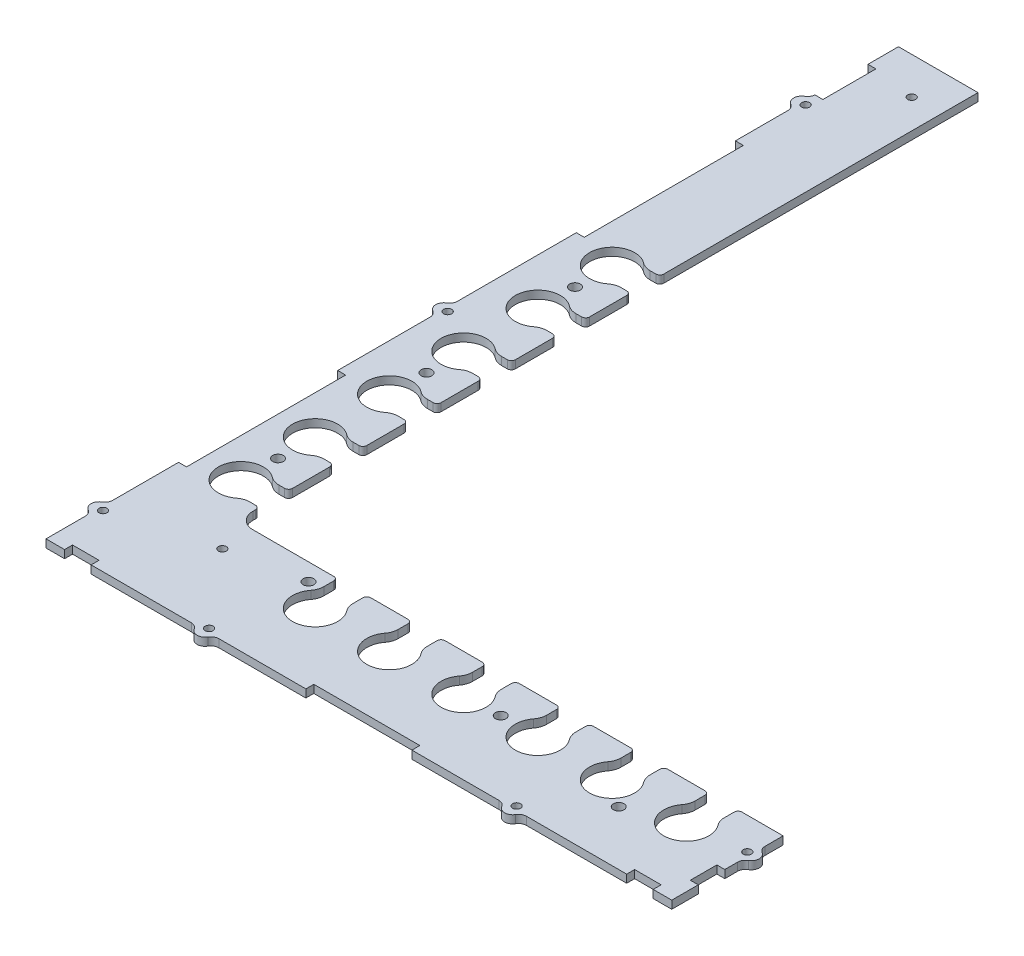
SolidWorks part; units mm, degrees
ref_plane "Спереди" through (0, 0, 0) normal (0, 0, 1) x (1, 0, 0)
ref_plane "Сверху" through (0, 0, 0) normal (0, 1, 0) x (1, 0, 0)
ref_plane "Справа" through (0, 0, 0) normal (1, 0, 0) x (0, 0, -1)
sketch "Эскиз1" plane through (0, 0, 0) normal (0, 1, 0) x (1, 0, 0)
  line L0 (0, 0) -> (0, 321.5)
  line L1 (0, 321.5) -> (30, 321.5)
  line L2 (30, 321.5) -> (30, 42)
  line L3 (30, 42) -> (236, 42)
  line L4 (236, 42) -> (236, 0)
  line L5 (236, 0) -> (0, 0)
  dimension "D1" = 321.5
  dimension "D2" = 236
  dimension "D3" = 42
  dimension "D4" = 30
extrude "Бобышка-Вытянуть1" add sketch "Эскиз1" along normal blind 3
sketch "Эскиз2" plane through (0, 3, 0) normal (0, 1, 0) x (1, 0, 0)
  line L0 (236, 0) -> (236, 42) construction
  line L1 (236, 10) -> (233, 10)
  line L2 (236, 10) -> (236, 20)
  line L3 (236, 20) -> (233, 20)
  line L4 (233, 10) -> (233, 20)
  dimension "D1" = 3
  dimension "D2" = 10
  dimension "D3" = 10
extrude "Вырез-Вытянуть1" cut sketch "Эскиз2" against normal blind 3
sketch "Эскиз4" plane through (236, 0, 0) normal (1, 0, 0) x (0, 0, -1)
  line L0 (20, 3) -> (42, 3) construction
  line L1 (20, 0) -> (42, 0) construction
  line L2 (30, 0) -> (33, 0)
  line L3 (30, 0) -> (30, 3)
  line L4 (30, 3) -> (33, 3)
  line L5 (33, 0) -> (33, 3)
  dimension "D1" = 30
  dimension "D2" = 3
revolve "Повернуть1" add sketch "Эскиз4" angle 360 about L3
fillet "Скругление1" radius 3 2 edges at (236, 1.5, -27) (236, 1.5, -33)
sketch "Эскиз5" plane through (0, 3, 0) normal (0, 1, 0) x (1, 0, 0)
  circle A0 centre (234.5, 30) radius 1.5
  dimension "D1" = 3
  dimension "D2" = 30
  dimension "D3" = 1.5
extrude "Вырез-Вытянуть2" cut sketch "Эскиз5" against normal blind 3
sketch "Эскиз6" plane through (0, 3, 0) normal (0, 1, 0) x (1, 0, 0)
  line L0 (0, 0) -> (236, 0) construction
  line L1 (229, 0) -> (219, 0)
  line L2 (229, 0) -> (229, 3)
  line L3 (229, 3) -> (219, 3)
  line L4 (219, 0) -> (219, 3)
  line L5 (118, 0) -> (118, 12.6976) construction
  line L6 (17, 0) -> (17, 3)
  line L7 (7, 3) -> (17, 3)
  line L8 (7, 0) -> (7, 3)
  line L9 (7, 0) -> (17, 0)
  dimension "D1" = 10
  dimension "D2" = 7
  dimension "D3" = 3
extrude "Вырез-Вытянуть3" cut sketch "Эскиз6" against normal blind 3
sketch "Эскиз7" plane through (0, 3, 0) normal (0, 1, 0) x (1, 0, 0)
  line L0 (17, 0) -> (219, 0) construction
  line L1 (98, 0) -> (138, 0)
  line L2 (98, 0) -> (98, 3)
  line L3 (98, 3) -> (138, 3)
  line L4 (138, 0) -> (138, 3)
  point P6 (118, 0)
  point P7 (118, 0)
  dimension "D1" = 40
  dimension "D2" = 3
extrude "Вырез-Вытянуть4" cut sketch "Эскиз7" against normal blind 3
sketch "Эскиз9" plane through (0, 3, 0) normal (0, 1, 0) x (1, 0, 0)
  line L0 (0, 321.5) -> (0, 0) construction
  line L1 (0, 50) -> (3, 50)
  line L2 (0, 50) -> (0, 110)
  line L3 (0, 110) -> (3, 110)
  line L4 (3, 50) -> (3, 110)
  line L5 (0, 0) -> (7, 0) construction
  line L6 (0, 200) -> (3, 200)
  line L7 (0, 200) -> (0, 260)
  line L8 (0, 260) -> (3, 260)
  line L9 (3, 200) -> (3, 260)
  line L10 (0, 290) -> (3, 290)
  line L11 (0, 290) -> (0, 310)
  line L12 (0, 310) -> (3, 310)
  line L13 (3, 290) -> (3, 310)
  point P16 (3.5, 0)
  dimension "D1" = 3
  dimension "D2" = 3
  dimension "D3" = 3
  dimension "D4" = 20
  dimension "D5" = 60
  dimension "D6" = 60
  dimension "D7" = 50
  dimension "D8" = 200
  dimension "D9" = 290
extrude "Вырез-Вытянуть5" cut sketch "Эскиз9" against normal blind 3
sketch "Эскиз11" plane through (0, 0, 0) normal (0, 0, 1) x (1, 0, 0)
  line L0 (17, 0) -> (98, 0) construction
  line L1 (60, 0) -> (63, 0)
  line L2 (60, 0) -> (60, 3)
  line L3 (60, 3) -> (63, 3)
  line L4 (63, 0) -> (63, 3)
  line L5 (17, 3) -> (98, 3) construction
  dimension "D1" = 3
  dimension "D2" = 60
revolve "Повернуть2" add sketch "Эскиз11" angle 360 about L2
sketch "Эскиз12" plane through (0, 0, 0) normal (0, 0, 1) x (1, 0, 0)
  line L0 (138, 0) -> (219, 0) construction
  line L1 (176, 0) -> (173, 0)
  line L2 (176, 0) -> (176, 3)
  line L3 (176, 3) -> (173, 3)
  line L4 (173, 0) -> (173, 3)
  line L5 (138, 3) -> (219, 3) construction
  dimension "D1" = 3
  dimension "D2" = 60
revolve "Повернуть3" add sketch "Эскиз12" angle 360 about L2
sketch "Эскиз13" plane through (0, 3, 0) normal (0, 1, 0) x (1, 0, 0)
  line L0 (17, 0) -> (57, 0) construction
  circle A0 centre (60, 1.5) radius 1.5
  circle A1 centre (176, 1.5) radius 1.5
  dimension "D1" = 3
  dimension "D2" = 60
  dimension "D3" = 1.5
  dimension "D4" = 60
extrude "Вырез-Вытянуть6" cut sketch "Эскиз13" against normal blind 3
fillet "Скругление2" radius 3 4 edges at (63, 1.5, 0) (57, 1.5, 0) (173, 1.5, 0) (179, 1.5, 0)
sketch "Эскиз14" plane through (0, 0, 0) normal (-1, 0, 0) x (0, 0, 1)
  line L0 (-290, 0) -> (-260, 0) construction
  line L1 (-288, 0) -> (-285, 0)
  line L2 (-288, 0) -> (-288, 3)
  line L3 (-288, 3) -> (-285, 3)
  line L4 (-285, 0) -> (-285, 3)
  line L6 (-290, 3) -> (-260, 3) construction
  dimension "D1" = 3
  dimension "D2" = 285
revolve "Повернуть4" add sketch "Эскиз14" angle 360 about L4
sketch "Эскиз15" plane through (0, 0, 0) normal (-1, 0, 0) x (0, 0, 1)
  line L0 (-200, 0) -> (-110, 0) construction
  line L1 (-153, 0) -> (-150, 0)
  line L2 (-153, 0) -> (-153, 3)
  line L3 (-153, 3) -> (-150, 3)
  line L4 (-150, 0) -> (-150, 3)
  line L5 (-200, 3) -> (-110, 3) construction
  dimension "D1" = 3
  dimension "D2" = 150
revolve "Повернуть5" add sketch "Эскиз15" angle 360 about L4
sketch "Эскиз16" plane through (0, 0, 0) normal (-1, 0, 0) x (0, 0, 1)
  line L0 (-50, 0) -> (0, 0) construction
  line L1 (-23, 0) -> (-20, 0)
  line L2 (-23, 0) -> (-23, 3)
  line L3 (-23, 3) -> (-20, 3)
  line L4 (-20, 0) -> (-20, 3)
  line L5 (-50, 3) -> (0, 3) construction
  dimension "D1" = 3
  dimension "D2" = 20
revolve "Повернуть6" add sketch "Эскиз16" angle 360 about L4
fillet "Скругление3" radius 3 6 edges at (0, 1.5, -288) (0, 1.5, -282) (0, 1.5, -147) (0, 1.5, -153) (0, 1.5, -23) (0, 1.5, -17)
sketch "Эскиз17" plane through (0, 3, 0) normal (0, 1, 0) x (1, 0, 0)
  circle A0 centre (1.5, 20) radius 1.5
  circle A1 centre (1.5, 150) radius 1.5
  circle A2 centre (1.5, 285) radius 1.5
  dimension "D1" = 3
  dimension "D2" = 20
  dimension "D3" = 1.5
  dimension "D4" = 150
  dimension "D5" = 285
extrude "Вырез-Вытянуть7" cut sketch "Эскиз17" against normal blind 3
sketch "Эскиз18" plane through (0, 3, 0) normal (0, 1, 0) x (1, 0, 0)
  line L0 (199.5, 62.1541) -> (199.5, -29.8225) construction
  line L1 (236, 35.1962) -> (236, 42) construction
  line L2 (236, 42) -> (30, 42) construction
  line L5 (208, 34.4807) -> (208, 42)
  line L6 (208, 42) -> (219, 42)
  line L7 (219, 34.4807) -> (219, 42)
  arc A0 (208, 34.4807) -> (219, 34.4807) centre (213.5, 28) ccw
  dimension "D2" = 17
  dimension "D1" = 36.5
  dimension "D3" = 14
  dimension "D4" = 14
  dimension "D5" = 11
extrude "Вырез-Вытянуть8" cut sketch "Эскиз18" against normal blind 3
fillet "Скругление9" radius 6 2 edges at (219, 1.5, -34.4807) (208, 1.5, -34.4807)
fillet "Скругление10" radius 1.5 2 edges at (208, 1.5, -42) (219, 1.5, -42)
pattern_linear "Линейный массив2" count 6 spacing 28 along (-1, 0, 0) of "Вырез-Вытянуть8", "Скругление10", "Скругление9"
sketch "Эскиз19" plane through (0, 3, 0) normal (0, 1, 0) x (1, 0, 0)
  line L0 (30, 42) -> (30, 321.5) construction
  line L2 (23.9807, 61.5) -> (30, 61.5)
  line L4 (23.9807, 50.5) -> (30, 50.5)
  line L5 (30, 61.5) -> (30, 50.5)
  arc A0 (23.9807, 61.5) -> (23.9807, 50.5) centre (17.5, 56) ccw
  dimension "D1" = 17
  dimension "D2" = 12.5
  dimension "D3" = 56
  dimension "D4" = 11
extrude "Вырез-Вытянуть9" cut sketch "Эскиз19" against normal blind 3
fillet "Скругление5" radius 6 2 edges at (23.9807, 1.5, -50.5) (23.9807, 1.5, -61.5)
fillet "Скругление7" radius 1.5 2 edges at (30, 1.5, -50.5) (30, 1.5, -61.5)
pattern_linear "Линейный массив3" count 6 spacing 28 along (0, 0, -1) of "Вырез-Вытянуть9", "Скругление5", "Скругление7"
sketch "Эскиз21" plane through (0, 3, 0) normal (0, 1, 0) x (1, 0, 0)
  arc A0 (206.7586, 33.1772) -> (220.2414, 33.1772) centre (213.5, 28) ccw construction
  circle A1 centre (143.5, 28) radius 2
  circle A3 centre (195.5, 20.5) radius 2
  circle A4 centre (63.5, 35.5) radius 2
  dimension "D1" = 4
  dimension "D6" = 80
  dimension "D3" = 18
  dimension "D7" = 7.5
  dimension "D2" = 52
  dimension "D4" = 7.5
  dimension "D5" = 7.5
extrude "Вырез-Вытянуть11" cut sketch "Эскиз21" against normal blind 3
sketch "Эскиз24" plane through (0, 3, 0) normal (0, 1, 0) x (1, 0, 0)
  line L0 (17, 0) -> (54.8038, 0) construction
  line L1 (0, 50) -> (0, 25.1962) construction
  circle A0 centre (36.5, 30) radius 1.5
  dimension "D1" = 3
  dimension "D2" = 30
  dimension "D3" = 36.5
extrude "Вырез-Вытянуть14" cut sketch "Эскиз24" against normal blind 3
fillet "Скругление8" radius 6 1 edges at (30, 1.5, -42)
sketch "Эскиз25" plane through (0, 3, 0) normal (0, 1, 0) x (1, 0, 0)
  line L0 (30, 63) -> (30, 77) construction
  circle A0 centre (17.5, 70) radius 2
  arc A2 (22.6772, 90.7414) -> (22.6772, 77.2586) centre (17.5, 84) ccw construction
  dimension "D1" = 4
  dimension "D2" = 12.5
  dimension "D3" = 14
extrude "Вырез-Вытянуть15" cut sketch "Эскиз25" against normal blind 10
pattern_linear "Линейный массив4" count 3 spacing 56 along (0, 0, -1) of "Вырез-Вытянуть15"
sketch "Эскиз26" plane through (0, 0, 0) normal (0, -1, 0) x (1, 0, 0)
  line L0 (17, 0) -> (54.8038, 0) construction
  line L1 (3, -290) -> (3, -310) construction
  circle A0 centre (19, -307.5) radius 1.5
  dimension "D1" = 3
  dimension "D2" = 307.5
  dimension "D3" = 16
extrude "Вырез-Вытянуть16" cut sketch "Эскиз26" against normal blind 3
